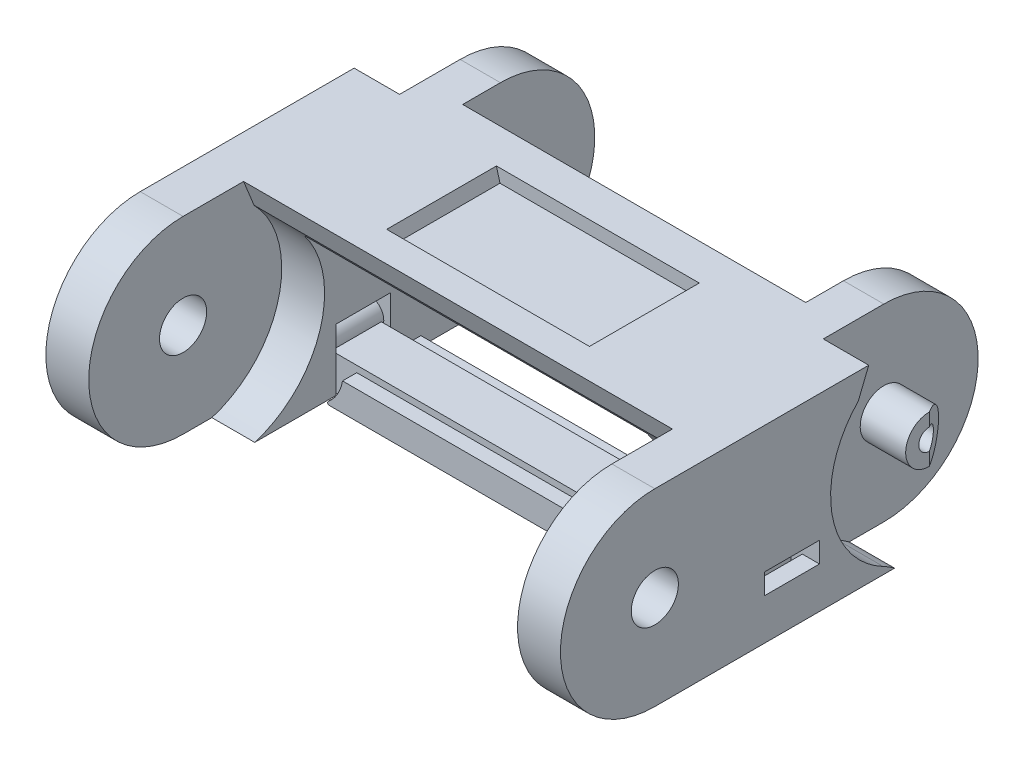
SolidWorks part; units mm, degrees
ref_plane "Front" through (0, 0, 0) normal (0, 0, 1) x (1, 0, 0)
ref_plane "Top" through (0, 0, 0) normal (0, 1, 0) x (1, 0, 0)
ref_plane "Right" through (0, 0, 0) normal (1, 0, 0) x (0, 0, -1)
ref_plane "Plane1" through (0, 0, 0) normal (0, 0, 1) x (1, 0, 0)
sketch "Sketch1" plane through (0, 0, 0) normal (0, 0, 1) x (1, 0, 0)
  line L0 (-30, -11) -> (30, -11)
  line L1 (30, -11) -> (30, 11)
  line L2 (30, 11) -> (-30, 11)
  line L3 (-30, 11) -> (-30, -11)
extrude "Boss-Extrude1" add sketch "Sketch1" against normal blind 54
ref_plane "Plane2" through (0, 0, 0) normal (0, 0, 1) x (1, 0, 0)
sketch "Sketch2" plane through (0, 0, 0) normal (0, 0, 1) x (1, 0, 0)
  line L0 (-20, -11) -> (20, -11)
  line L1 (20, -11) -> (20, 7)
  line L2 (20, 7) -> (-20, 7)
  line L3 (-20, 7) -> (-20, -11)
extrude "Cut-Extrude1" cut sketch "Sketch2" against normal blind 54 and the other way blind 54
ref_plane "Plane3" through (0, 0, -21.56) normal (0, 0, 1) x (1, 0, 0)
sketch "Sketch3" plane through (0, 0, -21.56) normal (0, 0, 1) x (1, 0, 0)
  line L0 (-12, 11.66) -> (-11.4105, 9.46)
  line L1 (-11.4105, 9.46) -> (11.4105, 9.46)
  line L2 (11.4105, 9.46) -> (12, 11.66)
  line L3 (12, 11.66) -> (-12, 11.66)
extrude "Cut-Extrude2" cut sketch "Sketch3" against normal blind 12.8
ref_plane "Plane4" through (0, 0, 0) normal (0, 1, 0) x (-1, 0, 0)
sketch "Sketch4" plane through (0, 0, 0) normal (0, 1, 0) x (-1, 0, 0)
  line L0 (60, -120) -> (60, 60)
  line L1 (60, 60) -> (-60, 60)
  line L2 (-60, 60) -> (-60, -120)
  line L3 (-60, -120) -> (60, -120)
  line L4 (30, -54) -> (30, 0)
  line L5 (30, 0) -> (20, 0)
  line L6 (20, 0) -> (20, -17.6)
  line L7 (20, -17.6) -> (-20, -17.6)
  line L8 (-20, -17.6) -> (-20, 0)
  line L9 (-20, 0) -> (-30, 0)
  line L10 (-30, 0) -> (-30, -54)
  line L11 (-30, -54) -> (-20, -54)
  line L12 (-20, -54) -> (-20, -38.6)
  line L13 (-20, -38.6) -> (20, -38.6)
  line L14 (20, -38.6) -> (20, -54)
  line L15 (20, -54) -> (30, -54)
extrude "Cut-Extrude3" cut sketch "Sketch4" against normal blind 54 and the other way blind 54
ref_plane "Plane5" through (0, 0, 0) normal (1, 0, 0) x (0, 0, -1)
sketch "Sketch5" plane through (0, 0, 0) normal (1, 0, 0) x (0, 0, -1)
  line L0 (-32, -32) -> (64, -32)
  line L1 (64, -32) -> (64, 32)
  line L2 (64, 32) -> (-32, 32)
  line L3 (-32, 32) -> (-32, -32)
  line L4 (11, -11) -> (43, -11)
  line L5 (43, 11) -> (11, 11)
  arc A0 (11, 11) -> (11, -11) centre (11, 0) ccw
  arc A1 (43, -11) -> (43, 11) centre (43, 0) ccw
extrude "Cut-Extrude4" cut sketch "Sketch5" against normal blind 30 and the other way blind 30
ref_plane "Plane6" through (-24.7, 0, 0) normal (1, 0, 0) x (0, 0, -1)
sketch "Sketch6" plane through (-24.7, 0, 0) normal (1, 0, 0) x (0, 0, -1)
  line L0 (43, -11.5) -> (43, -38)
  line L1 (43, -38) -> (63.2, -38)
  line L2 (63.2, -38) -> (63.2, 41)
  line L3 (63.2, 41) -> (48.0651, 41)
  line L4 (48.0651, 41) -> (34.7276, 7.9886)
  arc A0 (34.7276, 7.9886) -> (43, -11.5) centre (43, 0) ccw
  circle A1 centre (43, 0) radius 2.75
extrude "Cut-Extrude5" cut sketch "Sketch6" against normal blind 15
ref_plane "Plane7" through (-24.7, 0, 0) normal (1, 0, 0) x (0, 0, -1)
sketch "Sketch7" plane through (-24.7, 0, 0) normal (1, 0, 0) x (0, 0, -1)
  circle A0 centre (43, 0) radius 1.2222
extrude "Cut-Extrude6" cut sketch "Sketch7" against normal blind 15
ref_plane "Plane8" through (0, 0, 0) normal (1, 0, 0) x (0, 0, -1)
sketch "Sketch8" plane through (0, 0, 0) normal (1, 0, 0) x (0, 0, -1)
  circle A0 centre (11, 0) radius 2.75
extrude "Cut-Extrude7" cut sketch "Sketch8" against normal blind 30 and the other way blind 30
ref_plane "Plane9" through (-25, 0, 0) normal (1, 0, 0) x (0, 0, -1)
sketch "Sketch9" plane through (-25, 0, 0) normal (1, 0, 0) x (0, 0, -1)
  line L0 (-2.2, 26) -> (-2.2, -33)
  line L1 (-2.2, -33) -> (11, -33)
  line L2 (11, -33) -> (11, -11.5)
  line L3 (19.2724, 7.9886) -> (11.9953, 26)
  line L4 (11.9953, 26) -> (-2.2, 26)
  arc A0 (11, -11.5) -> (19.2724, 7.9886) centre (11, 0) ccw
extrude "Cut-Extrude8" cut sketch "Sketch9" along normal blind 50
ref_plane "Plane10" through (24.7, 0, 0) normal (1, 0, 0) x (0, 0, -1)
sketch "Sketch10" plane through (24.7, 0, 0) normal (1, 0, 0) x (0, 0, -1)
  line L0 (43, -19.0329) -> (43, -38)
  line L1 (43, -38) -> (63.2, -38)
  line L2 (63.2, -38) -> (63.2, 41)
  line L3 (63.2, 41) -> (48.0651, 41)
  line L4 (48.0651, 41) -> (34.7276, 7.9886)
  arc A0 (34.7276, 7.9886) -> (37.6512, -10.1804) centre (43, 0) ccw
  arc A1 (37.6512, -10.1804) -> (43, -19.0329) centre (33, -19.0329) cw
  circle A2 centre (43, 0) radius 2.75
extrude "Cut-Extrude9" cut sketch "Sketch10" along normal blind 15
ref_plane "Plane11" through (24.7, 0, 0) normal (1, 0, 0) x (0, 0, -1)
sketch "Sketch11" plane through (24.7, 0, 0) normal (1, 0, 0) x (0, 0, -1)
  circle A0 centre (43, 0) radius 1.2222
extrude "Cut-Extrude10" cut sketch "Sketch11" along normal blind 15
ref_plane "Plane12" through (0, 0, -27) normal (0, 0, 1) x (1, 0, 0)
sketch "Sketch12" plane through (0, 0, -27) normal (0, 0, 1) x (1, 0, 0)
  line L0 (-30, -6.2) -> (-28, -6.2)
  line L1 (-28, -6.2) -> (-28, -11)
  line L2 (-28, -11) -> (-20, -11)
  line L3 (-20, -11) -> (-20, -3.8)
  line L4 (-20, -3.8) -> (-30, -3.8)
  line L5 (-30, -3.8) -> (-30, -6.2)
  circle A0 centre (-22.5, -7) radius 1.7
extrude "Cut-Extrude11" cut sketch "Sketch12" against normal blind 3.2 and the other way blind 3.2
ref_plane "Plane13" through (0, 0, -27) normal (0, 0, 1) x (1, 0, 0)
sketch "Sketch13" plane through (0, 0, -27) normal (0, 0, 1) x (1, 0, 0)
  line L0 (20, -11) -> (28, -11)
  line L1 (28, -11) -> (28, -6.2)
  line L2 (28, -6.2) -> (30, -6.2)
  line L3 (30, -6.2) -> (30, -3.8)
  line L4 (30, -3.8) -> (20, -3.8)
  line L5 (20, -3.8) -> (20, -11)
  circle A0 centre (22.5, -7) radius 1.7
extrude "Cut-Extrude12" cut sketch "Sketch13" against normal blind 3.2 and the other way blind 3.2
ref_plane "Plane14" through (0, 0, 0) normal (0, 1, 0) x (-1, 0, 0)
sketch "Sketch14" plane through (0, 0, 0) normal (0, 1, 0) x (-1, 0, 0)
  line L0 (-28.3333, -45.75) -> (-30, -43)
  line L1 (-30, -43) -> (-30, -45.75)
  line L2 (-30, -45.75) -> (-28.3333, -45.75)
extrude "Cut-Extrude13" cut sketch "Sketch14" against normal blind 2.75 and the other way blind 2.75
ref_plane "Plane15" through (0, 0, 0) normal (0, 1, 0) x (-1, 0, 0)
sketch "Sketch15" plane through (0, 0, 0) normal (0, 1, 0) x (-1, 0, 0)
  line L0 (30, -45.75) -> (30, -43)
  line L1 (30, -43) -> (28.3333, -45.75)
  line L2 (28.3333, -45.75) -> (30, -45.75)
extrude "Cut-Extrude14" cut sketch "Sketch15" against normal blind 2.75 and the other way blind 2.75
ref_plane "Plane16" through (0, 0, -27) normal (0, 0, 1) x (1, 0, 0)
sketch "Sketch16" plane through (0, 0, -27) normal (0, 0, 1) x (1, 0, 0)
  line L0 (-23.4, -11) -> (23.4, -11)
  line L1 (27, -7.4) -> (27, -5)
  line L2 (27, -5) -> (24.2, -5)
  line L3 (24.2, -5) -> (24.2, -7)
  line L4 (20.8, -7) -> (-20.8, -7)
  line L5 (-24.2, -7) -> (-24.2, -5)
  line L6 (-24.2, -5) -> (-27, -5)
  line L7 (-27, -5) -> (-27, -7.4)
  arc A0 (-27, -7.4) -> (-23.4, -11) centre (-23.4, -7.4) ccw
  arc A1 (23.4, -11) -> (27, -7.4) centre (23.4, -7.4) ccw
  arc A2 (24.2, -7) -> (20.8, -7) centre (22.5, -7) cw
  arc A3 (-20.8, -7) -> (-24.2, -7) centre (-22.5, -7) cw
extrude "Boss-Extrude2" add sketch "Sketch16" against normal blind 2.9091 and the other way blind 2.9091
ref_plane "Plane17" through (0, 0, -27) normal (0, 0, 1) x (1, 0, 0)
sketch "Sketch17" plane through (0, 0, -27) normal (0, 0, 1) x (1, 0, 0)
  line L0 (-19.3796, -11) -> (19.3796, -11)
  line L1 (17.843, -7.75) -> (-17.843, -7.75)
  arc A0 (-19.5065, -10.6454) -> (-19.3796, -11) centre (-19.3796, -10.8) ccw
  arc A1 (19.3796, -11) -> (19.5065, -10.6454) centre (19.3796, -10.8) ccw
  arc A2 (19.5065, -10.6454) -> (17.843, -7.75) centre (22.5, -7) cw
  arc A3 (-17.843, -7.75) -> (-19.5065, -10.6454) centre (-22.5, -7) cw
extrude "Boss-Extrude3" add sketch "Sketch17" against normal blind 4.5714 and the other way blind 4.5714
